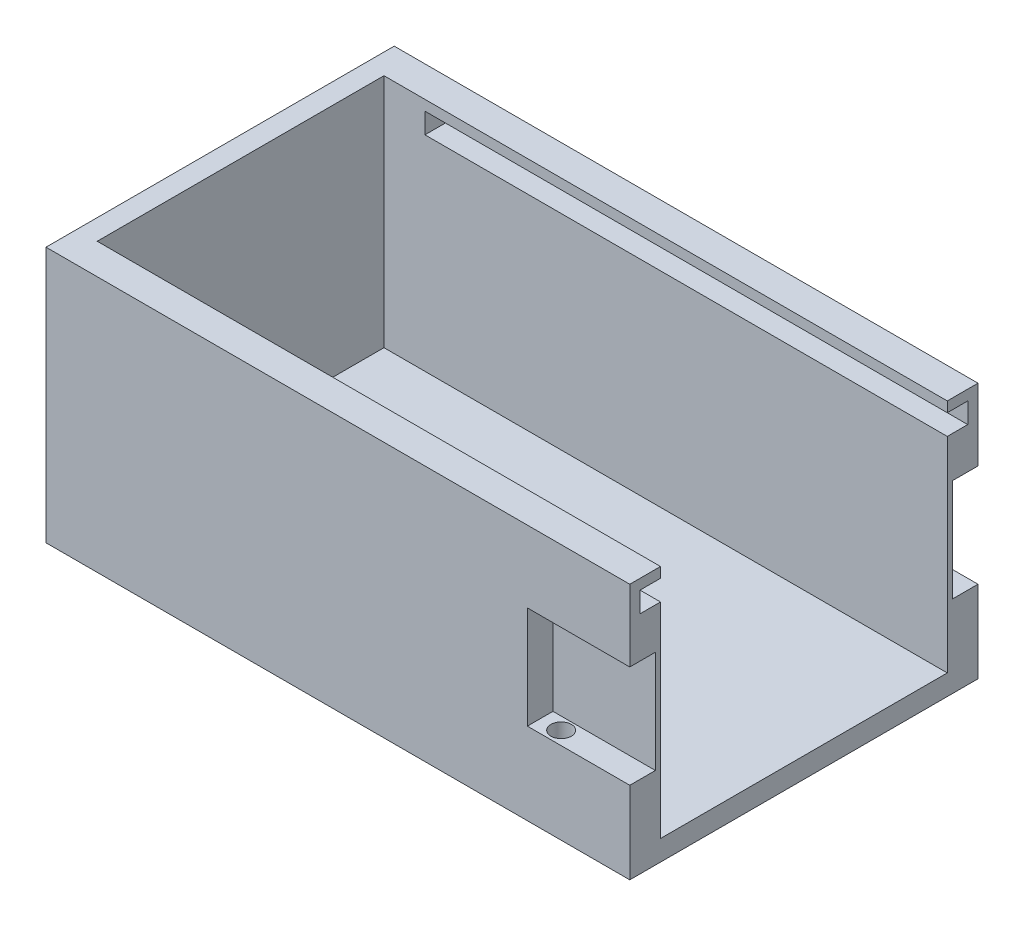
SolidWorks part; units mm, degrees
ref_plane "Front Plane" through (0, 0, 0) normal (0, 0, 1) x (1, 0, 0)
ref_plane "Top Plane" through (0, 0, 0) normal (0, 1, 0) x (1, 0, 0)
ref_plane "Right Plane" through (0, 0, 0) normal (1, 0, 0) x (0, 0, -1)
sketch "Sketch1" plane through (0, 0, 0) normal (0, 1, 0) x (1, 0, 0)
  line L1 (0, 0) -> (59, 0)
  line L2 (0, 0) -> (0, 34)
  line L3 (0, 34) -> (59, 34)
  line L4 (59, 0) -> (59, 34)
  line L5 (0, 0) -> (59, 34) construction
  line L6 (0, 34) -> (59, 0) construction
  line L7 (2, 3) -> (57, 3)
  line L8 (2, 3) -> (2, 31)
  line L9 (2, 31) -> (57, 31)
  line L10 (57, 3) -> (57, 31)
  line L11 (2, 3) -> (57, 31) construction
  line L12 (2, 31) -> (57, 3) construction
  point P4 (29.5, 17)
  point P6 (29.5, 17)
  dimension "D1" = 59
  dimension "D2" = 34
  dimension "D3" = 3
  dimension "D4" = 2
extrude "Boss-Extrude1" add sketch "Sketch1" along normal blind 25
extrude "Boss-Extrude2" add sketch "Sketch1<2>" along normal blind 2 contours L10 L9 L8 L7
sketch "Sketch1<2>" plane through (0, 0, 0) normal (0, 1, 0) x (1, 0, 0) same geometry as "Sketch1"
sketch "Sketch2" plane through (0, 25, 0) normal (0, 1, 0) x (1, 0, 0)
  line L0 (59, 34) -> (0, 34) construction
  line L1 (59, 0) -> (57, 0)
  line L2 (59, 0) -> (59, 34)
  line L3 (59, 34) -> (57, 34)
  line L4 (57, 0) -> (57, 34)
  line L5 (59, 0) -> (57, 34) construction
  line L6 (59, 34) -> (57, 0) construction
  point P4 (58, 17)
  dimension "D1" = 2
extrude "Cut-Extrude1" cut sketch "Sketch2" against normal blind 25
sketch "Sketch5" plane through (57, 0, 0) normal (1, 0, 0) x (0, 0, -1)
  line L0 (3, 25) -> (3, 2) construction
  line L1 (3, 24) -> (1, 24)
  line L2 (3, 24) -> (3, 22)
  line L3 (3, 22) -> (1, 22)
  line L4 (1, 24) -> (1, 22)
  line L5 (3, 24) -> (1, 22) construction
  line L6 (3, 22) -> (1, 24) construction
  line L7 (17, 0) -> (17, 18.6218) construction
  line L8 (3, 0) -> (31, 0) construction
  line L9 (3, 25) -> (0, 25) construction
  line L10 (31, 22) -> (33, 22)
  line L11 (33, 24) -> (33, 22)
  line L12 (31, 24) -> (33, 24)
  line L13 (31, 24) -> (31, 22)
  point P4 (2, 23)
  dimension "D1" = 2
  dimension "D2" = 2
  dimension "D3" = 1
extrude "Cut-Extrude4" cut sketch "Sketch5" against normal blind 51
sketch "Sketch9" plane through (0, 0, -34) normal (0, 0, -1) x (-1, 0, 0)
  line L0 (-57, 0) -> (-57, 25) construction
  line L1 (-57, 18) -> (-47, 18)
  line L2 (-57, 18) -> (-57, 8)
  line L3 (-57, 8) -> (-47, 8)
  line L4 (-47, 18) -> (-47, 8)
  line L5 (-57, 18) -> (-47, 8) construction
  line L6 (-57, 8) -> (-47, 18) construction
  line L7 (0, 0) -> (-59, 0) construction
  point P4 (-52, 13)
  dimension "D1" = 8
  dimension "D2" = 10
  dimension "D3" = 10
extrude "Cut-Extrude7" cut sketch "Sketch9" against normal blind 2.5
sketch "Sketch10" plane through (0, 0, 0) normal (0, 0, 1) x (1, 0, 0)
  line L0 (57, 0) -> (57, 25) construction
  line L1 (57, 18) -> (47, 18)
  line L2 (57, 18) -> (57, 8)
  line L3 (57, 8) -> (47, 8)
  line L4 (47, 18) -> (47, 8)
  line L5 (57, 18) -> (47, 8) construction
  line L6 (57, 8) -> (47, 18) construction
  line L7 (0, 0) -> (59, 0) construction
  point P4 (52, 13)
  dimension "D1" = 10
  dimension "D2" = 10
  dimension "D3" = 8
extrude "Cut-Extrude8" cut sketch "Sketch10" against normal blind 2.5
sketch "Sketch11" plane through (0, 18, 0) normal (0, -1, 0) x (-1, 0, 0)
  line L0 (-57, 2.5) -> (-47, 2.5) construction
  line L1 (-47, 2.5) -> (-47, 0) construction
  circle A0 centre (-49, 1.3) radius 1
  dimension "D1" = 2
  dimension "D2" = 1.2
  dimension "D3" = 2
extrude "Cut-Extrude9" cut sketch "Sketch11" against normal blind 2.5 and the other way blind 12.5
sketch "Sketch12" plane through (0, 18, 0) normal (0, -1, 0) x (-1, 0, 0)
  line L0 (-47, 31.5) -> (-47, 34) construction
  line L1 (-47, 31.5) -> (-57, 31.5) construction
  circle A0 centre (-48.8, 32.7) radius 1
  dimension "D2" = 2
  dimension "D1" = 1.8
  dimension "D3" = 1.2
extrude "Cut-Extrude10" cut sketch "Sketch12" against normal blind 2.5 and the other way blind 12.5
